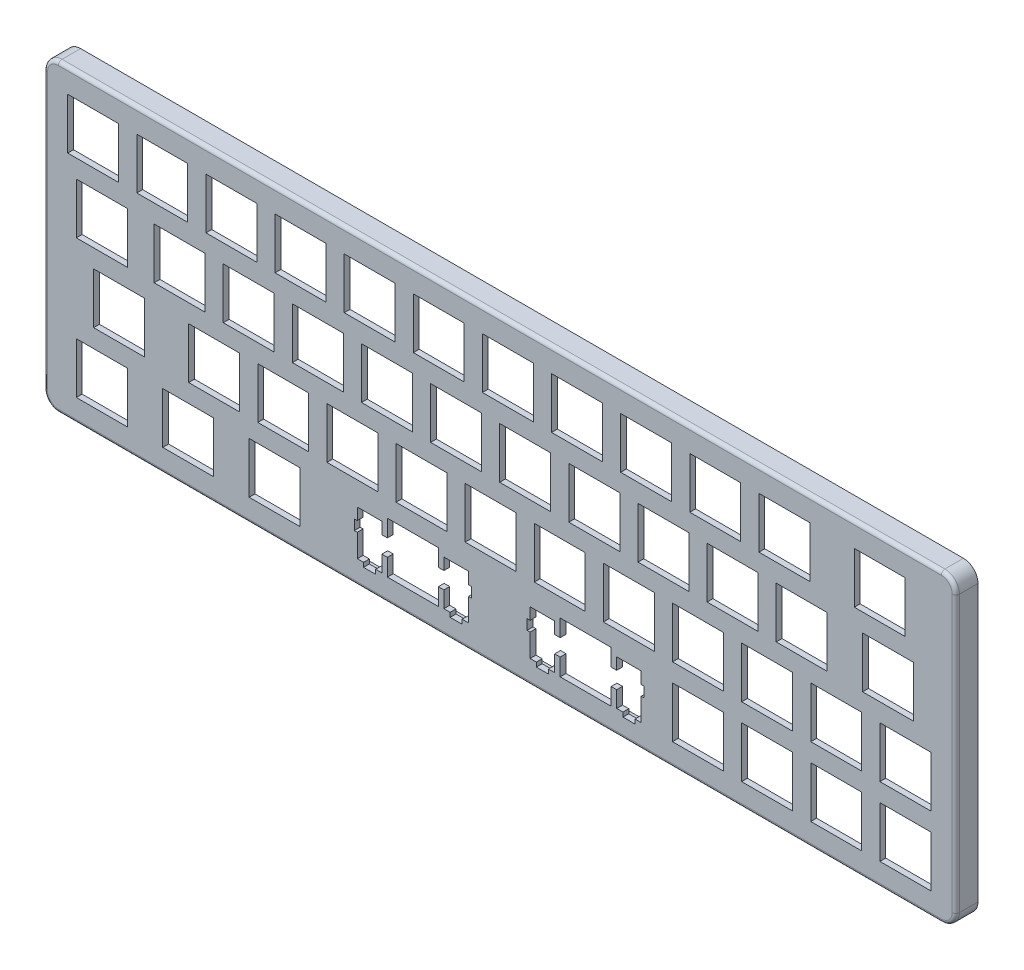
SolidWorks part; units mm, degrees
ref_plane "Front Plane" through (0, 0, 0) normal (0, 0, 1) x (1, 0, 0)
ref_plane "Top Plane" through (0, 0, 0) normal (0, 1, 0) x (1, 0, 0)
ref_plane "Right Plane" through (0, 0, 0) normal (1, 0, 0) x (0, 0, -1)
sketch "Sketch1" plane through (0, 0, 0) normal (0, 0, 1) x (1, 0, 0)
  line L5 (99.95, -106.45) -> (342.62, -106.45)
  line L6 (346.62, -110.45) -> (346.62, -186.25)
  line L7 (342.62, -190.25) -> (99.95, -190.25)
  line L8 (95.95, -110.45) -> (95.95, -186.25)
  line L9 (99.95, -107.95) -> (342.62, -107.95)
  line L10 (345.12, -110.45) -> (345.12, -186.25)
  line L11 (342.62, -188.75) -> (99.95, -188.75)
  line L12 (97.45, -186.25) -> (97.45, -110.45)
  circle A0 centre (147.5, -114.3) radius 1.1
  circle A1 centre (325.72, -114.3) radius 1.1
  circle A2 centre (332.75, -171.3) radius 1.1
  circle A3 centre (218.75, -152.3) radius 1.1138
  circle A4 centre (111.875, -171.3) radius 1.106
  arc A9 (95.95, -110.45) -> (99.95, -106.45) centre (99.95, -110.45) cw
  arc A10 (342.62, -106.45) -> (346.62, -110.45) centre (342.62, -110.45) cw
  arc A11 (346.62, -186.25) -> (342.62, -190.25) centre (342.62, -186.25) cw
  arc A12 (99.95, -190.25) -> (95.95, -186.25) centre (99.95, -186.25) cw
  arc A13 (97.45, -110.45) -> (99.95, -107.95) centre (99.95, -110.45) cw
  arc A14 (342.62, -107.95) -> (345.12, -110.45) centre (342.62, -110.45) cw
  arc A15 (345.12, -186.25) -> (342.62, -188.75) centre (342.62, -186.25) cw
  arc A16 (99.95, -188.75) -> (97.45, -186.25) centre (99.95, -186.25) cw
  dimension "D2" = 1.5
  dimension "D1" = 242.67
  dimension "D3" = 75.8
sketch "Sketch3" plane through (0, 0, 0) normal (0, 0, 1) x (1, 0, 0)
  line B0 (230.5, -113) -> (216.5, -113)
  line B1 (211.5, -127) -> (211.5, -113)
  line B2 (197.5, -113) -> (197.5, -127)
  line B3 (197.25, -132) -> (183.25, -132)
  line B4 (202.25, -146) -> (216.25, -146)
  line B5 (202.25, -132) -> (202.25, -146)
  line B6 (287.75, -170) -> (287.75, -184)
  line B7 (268.75, -165) -> (282.75, -165)
  line B8 (268.75, -151) -> (268.75, -165)
  line B9 (263.75, -151) -> (249.75, -151)
  line B10 (282.75, -151) -> (268.75, -151)
  line B11 (297.25, -146) -> (311.25, -146)
  line B12 (321, -146) -> (335, -146)
  line B13 (297.25, -132) -> (297.25, -146)
  line B14 (292.25, -146) -> (292.25, -132)
  line B15 (278.25, -132) -> (278.25, -146)
  line B16 (273.25, -146) -> (273.25, -132)
  line B17 (259.25, -132) -> (259.25, -146)
  line B18 (254.25, -146) -> (254.25, -132)
  line B19 (240.25, -146) -> (254.25, -146)
  line B20 (235.25, -132) -> (221.25, -132)
  line B21 (221.25, -146) -> (235.25, -146)
  line B22 (230.75, -165) -> (244.75, -165)
  line B23 (251.875, -170) -> (237.875, -170)
  line B24 (237.875, -170) -> (237.875, -184)
  line B25 (244.75, -165) -> (244.75, -151)
  line B26 (244.75, -151) -> (230.75, -151)
  line B27 (235.25, -146) -> (235.25, -132)
  line B28 (235.5, -113) -> (235.5, -127)
  line B29 (320.75, -184) -> (320.75, -170)
  line B30 (320.75, -170) -> (306.75, -170)
  line B31 (263.75, -165) -> (263.75, -151)
  line B32 (249.75, -151) -> (249.75, -165)
  line B33 (230.75, -151) -> (230.75, -165)
  line B34 (225.75, -165) -> (225.75, -151)
  line B35 (192.75, -151) -> (192.75, -165)
  line B36 (173.75, -165) -> (187.75, -165)
  line B37 (154.75, -165) -> (168.75, -165)
  line B38 (135.75, -165) -> (149.75, -165)
  line B39 (109.625, -165) -> (123.625, -165)
  line B40 (190.375, -184) -> (204.375, -184)
  line B41 (204.375, -184) -> (204.375, -170)
  line B42 (211.75, -151) -> (211.75, -165)
  line B43 (225.75, -151) -> (211.75, -151)
  line B44 (183.25, -146) -> (197.25, -146)
  line B45 (164.25, -132) -> (164.25, -146)
  line B46 (159.25, -146) -> (159.25, -132)
  line B47 (145.25, -132) -> (145.25, -146)
  line B48 (140.25, -146) -> (140.25, -132)
  line B49 (140.25, -132) -> (126.25, -132)
  line B50 (121.5, -127) -> (135.5, -127)
  line B51 (135.5, -113) -> (121.5, -113)
  line B52 (149.75, -151) -> (135.75, -151)
  line B53 (126.25, -146) -> (140.25, -146)
  line B54 (126.25, -132) -> (126.25, -146)
  line B55 (249.5, -127) -> (249.5, -113)
  line B56 (268.5, -127) -> (268.5, -113)
  line B57 (287.5, -113) -> (273.5, -113)
  line B58 (292.5, -113) -> (292.5, -127)
  line B59 (306.5, -127) -> (306.5, -113)
  line B60 (318.72, -127) -> (332.72, -127)
  line B61 (311.25, -146) -> (311.25, -132)
  line B62 (221.25, -132) -> (221.25, -146)
  line B63 (216.25, -146) -> (216.25, -132)
  line B64 (183.25, -132) -> (183.25, -146)
  line B65 (178.25, -146) -> (178.25, -132)
  line B66 (164.25, -146) -> (178.25, -146)
  line B67 (145.25, -146) -> (159.25, -146)
  line B68 (168.75, -151) -> (154.75, -151)
  line B69 (187.75, -151) -> (173.75, -151)
  line B70 (206.75, -165) -> (206.75, -151)
  line B71 (211.75, -165) -> (225.75, -165)
  line B72 (173.75, -151) -> (173.75, -165)
  line B73 (168.75, -165) -> (168.75, -151)
  line B74 (149.75, -165) -> (149.75, -151)
  line B75 (135.75, -151) -> (135.75, -165)
  line B76 (159.25, -132) -> (145.25, -132)
  line B77 (178.5, -113) -> (178.5, -127)
  line B78 (192.5, -113) -> (178.5, -113)
  line B79 (142.625, -170) -> (128.625, -170)
  line B80 (118.875, -184) -> (118.875, -170)
  line B81 (104.875, -170) -> (104.875, -184)
  line B82 (118.875, -170) -> (104.875, -170)
  line B83 (204.375, -170) -> (190.375, -170)
  line B84 (166.375, -184) -> (166.375, -170)
  line B85 (166.375, -170) -> (152.375, -170)
  line B86 (128.625, -170) -> (128.625, -184)
  line B87 (154.75, -151) -> (154.75, -165)
  line B88 (116.5, -127) -> (116.5, -113)
  line B89 (211.5, -113) -> (197.5, -113)
  line B90 (197.5, -127) -> (211.5, -127)
  line B91 (216.25, -132) -> (202.25, -132)
  line B92 (206.75, -151) -> (192.75, -151)
  line B93 (187.75, -165) -> (187.75, -151)
  line B94 (282.75, -184) -> (282.75, -170)
  line B95 (282.75, -170) -> (268.75, -170)
  line B96 (249.75, -165) -> (263.75, -165)
  line B97 (292.25, -132) -> (278.25, -132)
  line B98 (311.25, -132) -> (297.25, -132)
  line B99 (135.5, -127) -> (135.5, -113)
  line B100 (140.5, -113) -> (140.5, -127)
  line B101 (140.5, -127) -> (154.5, -127)
  line B102 (102.5, -113) -> (102.5, -127)
  line B103 (102.5, -127) -> (116.5, -127)
  line B104 (121.5, -113) -> (121.5, -127)
  line B105 (154.5, -113) -> (140.5, -113)
  line B106 (306.75, -184) -> (320.75, -184)
  line B107 (306.75, -170) -> (306.75, -184)
  line B108 (301.75, -184) -> (301.75, -170)
  line B109 (99.95, -106.45) -> (342.62, -106.45)
  line B110 (154.5, -127) -> (154.5, -113)
  line B111 (173.5, -113) -> (159.5, -113)
  line B112 (95.95, -186.25) -> (95.95, -110.45)
  line B113 (346.62, -110.45) -> (346.62, -186.25)
  line B114 (342.62, -190.25) -> (99.95, -190.25)
  line B115 (116.5, -113) -> (102.5, -113)
  line B116 (159.5, -127) -> (173.5, -127)
  line B117 (173.5, -127) -> (173.5, -113)
  line B118 (159.5, -113) -> (159.5, -127)
  line B119 (178.5, -127) -> (192.5, -127)
  line B120 (192.5, -127) -> (192.5, -113)
  line B121 (216.5, -127) -> (230.5, -127)
  line B122 (230.5, -127) -> (230.5, -113)
  line B123 (216.5, -113) -> (216.5, -127)
  line B124 (235.5, -127) -> (249.5, -127)
  line B125 (249.5, -113) -> (235.5, -113)
  line B126 (254.5, -127) -> (268.5, -127)
  line B127 (268.5, -113) -> (254.5, -113)
  line B128 (254.5, -113) -> (254.5, -127)
  line B129 (273.5, -127) -> (287.5, -127)
  line B130 (287.5, -127) -> (287.5, -113)
  line B131 (273.5, -113) -> (273.5, -127)
  line B132 (292.5, -127) -> (306.5, -127)
  line B133 (306.5, -113) -> (292.5, -113)
  line B134 (332.72, -127) -> (332.72, -113)
  line B135 (332.72, -113) -> (318.72, -113)
  line B136 (318.72, -113) -> (318.72, -127)
  line B137 (104.875, -146) -> (118.875, -146)
  line B138 (118.875, -146) -> (118.875, -132)
  line B139 (118.875, -132) -> (104.875, -132)
  line B140 (104.875, -132) -> (104.875, -146)
  line B141 (178.25, -132) -> (164.25, -132)
  line B142 (197.25, -146) -> (197.25, -132)
  line B143 (254.25, -132) -> (240.25, -132)
  line B144 (240.25, -132) -> (240.25, -146)
  line B145 (259.25, -146) -> (273.25, -146)
  line B146 (273.25, -132) -> (259.25, -132)
  line B147 (278.25, -146) -> (292.25, -146)
  line B148 (335, -146) -> (335, -132)
  line B149 (335, -132) -> (321, -132)
  line B150 (321, -132) -> (321, -146)
  line B151 (123.625, -165) -> (123.625, -151)
  line B152 (123.625, -151) -> (109.625, -151)
  line B153 (109.625, -151) -> (109.625, -165)
  line B154 (192.75, -165) -> (206.75, -165)
  line B155 (282.75, -165) -> (282.75, -151)
  line B156 (287.75, -165) -> (301.75, -165)
  line B157 (301.75, -165) -> (301.75, -151)
  line B158 (301.75, -151) -> (287.75, -151)
  line B159 (287.75, -151) -> (287.75, -165)
  line B160 (306.75, -165) -> (320.75, -165)
  line B161 (320.75, -165) -> (320.75, -151)
  line B162 (320.75, -151) -> (306.75, -151)
  line B163 (306.75, -151) -> (306.75, -165)
  line B164 (325.75, -165) -> (339.75, -165)
  line B165 (339.75, -165) -> (339.75, -151)
  line B166 (339.75, -151) -> (325.75, -151)
  line B167 (325.75, -151) -> (325.75, -165)
  line B168 (104.875, -184) -> (118.875, -184)
  line B169 (128.625, -184) -> (142.625, -184)
  line B170 (142.625, -184) -> (142.625, -170)
  line B171 (152.375, -184) -> (166.375, -184)
  line B172 (152.375, -170) -> (152.375, -184)
  line B173 (190.375, -170) -> (190.375, -184)
  line B174 (237.875, -184) -> (251.875, -184)
  line B175 (251.875, -184) -> (251.875, -170)
  line B176 (268.75, -184) -> (282.75, -184)
  line B177 (268.75, -170) -> (268.75, -184)
  line B178 (287.75, -184) -> (301.75, -184)
  line B179 (301.75, -170) -> (287.75, -170)
  line B180 (325.75, -184) -> (339.75, -184)
  line B181 (339.75, -184) -> (339.75, -170)
  line B182 (339.75, -170) -> (325.75, -170)
  line B183 (325.75, -170) -> (325.75, -184)
  arc B184 (99.95, -106.45) -> (95.95, -110.45) centre (99.95, -110.45) ccw
  arc B185 (346.62, -110.45) -> (342.62, -106.45) centre (342.62, -110.45) ccw
  arc B186 (342.62, -190.25) -> (346.62, -186.25) centre (342.62, -186.25) ccw
  arc B187 (95.95, -186.25) -> (99.95, -190.25) centre (99.95, -186.25) ccw
  line B188 (205.9044, -183.7589) -> (205.9044, -179.2889)
  line B189 (207.6294, -183.7589) -> (205.9044, -183.7589)
  line B190 (207.6294, -184.9589) -> (207.6294, -183.7589)
  line B191 (210.9294, -184.9589) -> (207.6294, -184.9589)
  line B192 (210.9294, -183.7589) -> (210.9294, -184.9589)
  line B193 (212.6544, -183.7589) -> (210.9294, -183.7589)
  line B194 (212.6544, -177.4739) -> (212.6544, -183.7589)
  line B195 (213.4794, -177.4739) -> (212.6544, -177.4739)
  line B196 (213.4794, -174.6889) -> (213.4794, -177.4739)
  line B197 (212.6544, -174.6889) -> (213.4794, -174.6889)
  line B198 (212.6544, -171.4589) -> (212.6544, -174.6889)
  line B199 (205.9044, -171.4589) -> (212.6544, -171.4589)
  line B200 (205.9044, -174.6889) -> (205.9044, -171.4589)
  line B201 (204.3794, -174.6889) -> (205.9044, -174.6889)
  line B202 (204.3794, -169.9889) -> (204.3794, -174.6889)
  line B203 (204.3794, -169.9889) -> (190.3794, -169.9889)
  line B204 (190.3794, -174.6889) -> (188.8544, -174.6889)
  line B205 (188.8544, -174.6889) -> (188.8544, -171.4589)
  line B206 (188.8544, -171.4589) -> (182.1044, -171.4589)
  line B207 (182.1044, -171.4589) -> (182.1044, -174.6889)
  line B208 (182.1044, -174.6889) -> (181.2794, -174.6889)
  line B209 (205.9044, -179.2889) -> (204.3794, -179.2889)
  line B210 (187.1294, -183.7589) -> (188.8544, -183.7589)
  line B211 (188.8544, -183.7589) -> (188.8544, -179.2889)
  line B212 (188.8544, -179.2889) -> (190.3794, -179.2889)
  line B213 (190.3794, -179.2889) -> (190.3794, -183.9889)
  line B214 (181.2794, -174.6889) -> (181.2794, -177.4739)
  line B215 (181.2794, -177.4739) -> (182.1044, -177.4739)
  line B216 (182.1044, -177.4739) -> (182.1044, -183.7589)
  line B217 (182.1044, -183.7589) -> (183.8294, -183.7589)
  line B218 (183.8294, -183.7589) -> (183.8294, -184.9589)
  line B219 (183.8294, -184.9589) -> (187.1294, -184.9589)
  line B220 (187.1294, -184.9589) -> (187.1294, -183.7589)
  line B221 (204.3794, -179.2889) -> (204.3794, -183.9889)
  line B222 (190.3794, -169.9889) -> (190.3794, -174.6889)
  line B223 (204.3794, -183.9889) -> (190.3794, -183.9889)
  line B224 (253.4033, -183.7589) -> (253.4033, -179.2889)
  line B225 (255.1283, -183.7589) -> (253.4033, -183.7589)
  line B226 (255.1283, -184.9589) -> (255.1283, -183.7589)
  line B227 (258.4283, -184.9589) -> (255.1283, -184.9589)
  line B228 (258.4283, -183.7589) -> (258.4283, -184.9589)
  line B229 (260.1533, -183.7589) -> (258.4283, -183.7589)
  line B230 (260.1533, -177.4739) -> (260.1533, -183.7589)
  line B231 (260.9783, -177.4739) -> (260.1533, -177.4739)
  line B232 (260.9783, -174.6889) -> (260.9783, -177.4739)
  line B233 (260.1533, -174.6889) -> (260.9783, -174.6889)
  line B234 (260.1533, -171.4589) -> (260.1533, -174.6889)
  line B235 (253.4033, -171.4589) -> (260.1533, -171.4589)
  line B236 (253.4033, -174.6889) -> (253.4033, -171.4589)
  line B237 (251.8783, -174.6889) -> (253.4033, -174.6889)
  line B238 (251.8783, -169.9889) -> (251.8783, -174.6889)
  line B239 (251.8783, -169.9889) -> (237.8783, -169.9889)
  line B240 (237.8783, -174.6889) -> (236.3533, -174.6889)
  line B241 (236.3533, -174.6889) -> (236.3533, -171.4589)
  line B242 (236.3533, -171.4589) -> (229.6033, -171.4589)
  line B243 (229.6033, -171.4589) -> (229.6033, -174.6889)
  line B244 (229.6033, -174.6889) -> (228.7783, -174.6889)
  line B245 (253.4033, -179.2889) -> (251.8783, -179.2889)
  line B246 (234.6283, -183.7589) -> (236.3533, -183.7589)
  line B247 (236.3533, -183.7589) -> (236.3533, -179.2889)
  line B248 (236.3533, -179.2889) -> (237.8783, -179.2889)
  line B249 (237.8783, -179.2889) -> (237.8783, -183.9889)
  line B250 (228.7783, -174.6889) -> (228.7783, -177.4739)
  line B251 (228.7783, -177.4739) -> (229.6033, -177.4739)
  line B252 (229.6033, -177.4739) -> (229.6033, -183.7589)
  line B253 (229.6033, -183.7589) -> (231.3283, -183.7589)
  line B254 (231.3283, -183.7589) -> (231.3283, -184.9589)
  line B255 (231.3283, -184.9589) -> (234.6283, -184.9589)
  line B256 (234.6283, -184.9589) -> (234.6283, -183.7589)
  line B257 (251.8783, -179.2889) -> (251.8783, -183.9889)
  line B258 (237.8783, -169.9889) -> (237.8783, -174.6889)
  line B259 (251.8783, -183.9889) -> (237.8783, -183.9889)
sketch_block_instance "switch_plate (3)-1"
sketch_block "switch_plate (3)"
sketch_block_instance "platemountstabv2-1"
sketch_block "platemountstabv2"
sketch_block_instance "platemountstabv2-2"
extrude "Boss-Extrude1" add sketch "Sketch3" along normal blind 1.6 contours B112 B187 B114 B186 B113 B185 B109 B184 B102 B115 B88 B103 B104 B51 B99 B50 B100 B105 B110 B101 B118 B111 B117 B116 B77 B78 B120 B119 B2 B89 B1 B90 B123 B0 B122 B121 B28 B125 B55 B124 B128 B127 region at (220.5788, -148.6962, 0)
extrude "Boss-Extrude2" add sketch "Sketch1" against normal blind 4.5 contours A12 L7 A11 L6 A10 L5 A9 L8 region at (221.285, -106.7143, 0)
fillet "Fillet2" radius 1 8 edges at (97.1216, -107.6216, 1.6) (95.95, -148.35, 1.6) (97.1216, -189.0784, 1.6) (221.285, -190.25, 1.6) (345.4484, -189.0784, 1.6) (346.62, -148.35, 1.6) (345.4484, -107.6216, 1.6) (221.285, -106.45, 1.6)
